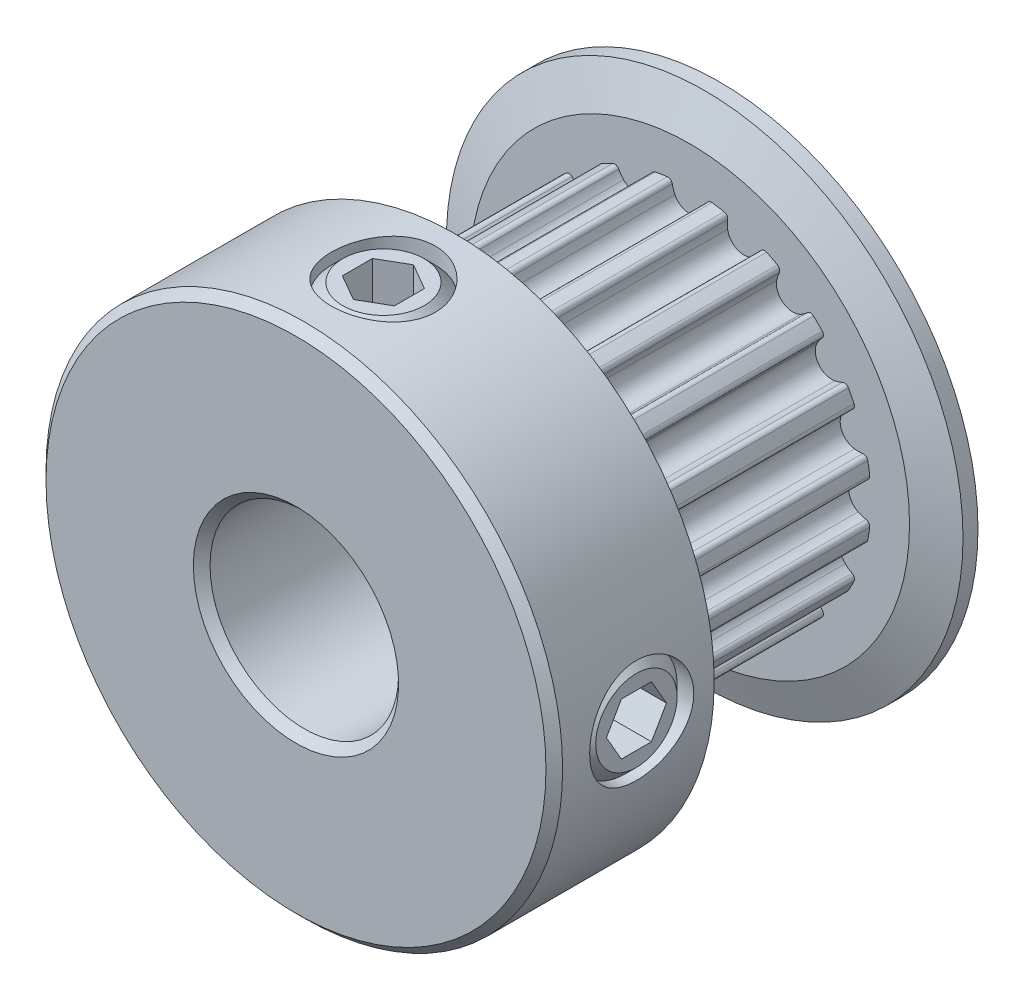
SolidWorks part; units mm, degrees
ref_plane "Front Plane" through (0, 0, 0) normal (0, 0, 1) x (1, 0, 0)
ref_plane "Top Plane" through (0, 0, 0) normal (0, 1, 0) x (1, 0, 0)
ref_plane "Right Plane" through (0, 0, 0) normal (1, 0, 0) x (0, 0, -1)
sketch "Sketch1" plane through (0, 0, 0) normal (0, 0, 1) x (1, 0, 0)
  line L1 (-1.7499, 5.3585) -> (1.7499, 5.3585) construction
  line L4 (0, 0) -> (0, 5.3585) construction
  line L5 (0, 5.3585) -> (0, 11.2045) construction
  line L6 (0, 6.3625) -> (1.9751, 6.0482) construction
  line L7 (1.9751, 6.0482) -> (2.6648, 5.8229) construction
  line L8 (1.9751, 6.0482) -> (1.7499, 5.3585) construction
  line L9 (-1.9751, 6.0482) -> (-1.7499, 5.3585) construction
  line L10 (-1.8963, 5.8067) -> (-2.841, 8.6995)
  line L11 (-2.841, 8.6995) -> (2.841, 8.6995)
  line L12 (2.841, 8.6995) -> (1.8963, 5.8067)
  circle A0 centre (0, 0) radius 6.3625 construction
  circle A1 centre (0, 0) radius 8.6995 construction
  circle A2 centre (0, 0) radius 6.1085 construction
  arc A3 (-0.4989, 5.6703) -> (0.4989, 5.6703) centre (0, 5.9135) ccw
  arc A4 (-0.4989, 5.6703) -> (-0.5855, 5.9387) centre (0.4, 6.1085) cw
  arc A5 (-1.8963, 5.8067) -> (-0.7518, 6.0621) centre (0, 0) cw
  arc A6 (-0.5855, 5.9387) -> (-0.7518, 6.0621) centre (-0.7333, 5.9132) ccw
  arc A7 (1.8963, 5.8067) -> (0.7518, 6.0621) centre (0, 0) ccw
  arc A8 (0.5855, 5.9387) -> (0.7518, 6.0621) centre (0.7333, 5.9132) cw
  arc A9 (0.4989, 5.6703) -> (0.5855, 5.9387) centre (-0.4, 6.1085) ccw
  point P6 (0, 20.9083)
  point P11 (0, 6.3625)
  point P13 (0, 8.6995)
  point P14 (0, 6.1085)
  dimension "D1" = 9.7038
  dimension "D2" = 4.842
sketch "Sketch2" plane through (0, 0, 0) normal (1, 0, 0) x (0, 0, -1)
  line L0 (-7.135, 3.175) -> (7.135, 3.175)
  line L1 (-7.135, 3.175) -> (-7.135, 8.6995)
  line L2 (-1.75, 8.6995) -> (-7.135, 8.6995)
  line L3 (-2.255, 3.175) -> (-2.255, 8.6995) construction
  line L4 (-2.255, 8.6995) -> (-1.245, 8.6995) construction
  line L5 (-1.245, 8.6995) -> (-1.245, 6.1085) construction
  line L6 (-1.245, 6.1085) -> (6.125, 6.1085)
  line L7 (6.125, 6.1085) -> (6.125, 8.6995) construction
  line L8 (6.125, 8.6995) -> (7.135, 8.6995) construction
  line L9 (7.135, 8.6995) -> (7.135, 3.175)
  line L10 (-7.135, 0) -> (7.135, 0) construction
  line L11 (6.63, 8.6995) -> (6.125, 7.404)
  line L12 (-1.245, 7.404) -> (-1.75, 8.6995)
  line L14 (-1.245, 7.404) -> (-1.245, 6.1085)
  line L15 (6.125, 6.1085) -> (6.125, 7.404)
  line L16 (6.63, 8.6995) -> (7.135, 8.6995)
  arc A0 (-1.245, 7.404) -> (-1.75, 8.6995) centre (-3.1592, 7.404) ccw construction
  arc A1 (6.125, 7.404) -> (6.63, 8.6995) centre (8.0392, 7.404) cw construction
  point P12 (-1.245, 7.404)
  point P14 (-1.75, 8.6995)
  point P20 (6.125, 7.404)
  point P21 (6.63, 8.6995)
  point P25 (6.125, 0)
  point P26 (-1.245, 0)
  dimension "OA" = 14.27
  dimension "Bore" = 6.35
  dimension "Outside Width" = 8.38
  dimension "Inside Width" = 7.37
revolve "Revolve1" add sketch "Sketch2" angle 360 mid plane about L10
sketch "Sketch3" plane through (0, 0, 0) normal (0, 0, 1) x (1, 0, 0)
  line L6 (2.841, 8.6995) -> (-2.841, 8.6995)
  line L7 (1.8963, 5.8067) -> (2.841, 8.6995)
  line L8 (-2.841, 8.6995) -> (-1.8963, 5.8067)
  line L9 (2.841, 8.6995) -> (-2.841, 8.6995)
  line L10 (1.8963, 5.8067) -> (2.841, 8.6995)
  line L11 (-2.841, 8.6995) -> (-1.8963, 5.8067)
  arc A8 (1.8963, 5.8067) -> (0.7518, 6.0621) centre (0, 0) ccw
  arc A9 (0.7518, 6.0621) -> (0.5855, 5.9387) centre (0.7333, 5.9132) ccw
  arc A10 (0.4989, 5.6703) -> (0.5855, 5.9387) centre (-0.4, 6.1085) ccw
  arc A11 (-0.4989, 5.6703) -> (0.4989, 5.6703) centre (0, 5.9135) ccw
  arc A12 (-0.5855, 5.9387) -> (-0.4989, 5.6703) centre (0.4, 6.1085) ccw
  arc A13 (-0.5855, 5.9387) -> (-0.7518, 6.0621) centre (-0.7333, 5.9132) ccw
  arc A14 (-0.7518, 6.0621) -> (-1.8963, 5.8067) centre (0, 0) ccw
  arc A15 (1.8963, 5.8067) -> (0.7518, 6.0621) centre (0, 0) ccw
  arc A16 (0.7518, 6.0621) -> (0.5855, 5.9387) centre (0.7333, 5.9132) ccw
  arc A17 (0.4989, 5.6703) -> (0.5855, 5.9387) centre (-0.4, 6.1085) ccw
  arc A18 (-0.4989, 5.6703) -> (0.4989, 5.6703) centre (0, 5.9135) ccw
  arc A19 (-0.5855, 5.9387) -> (-0.4989, 5.6703) centre (0.4, 6.1085) ccw
  arc A20 (-0.5855, 5.9387) -> (-0.7518, 6.0621) centre (-0.7333, 5.9132) ccw
  arc A21 (-0.7518, 6.0621) -> (-1.8963, 5.8067) centre (0, 0) ccw
  dimension "D1" = 0
extrude "Cut-Extrude1" cut sketch "Sketch3" against normal up to vertex (6.125 mm away) from vertex up to point (0, 6.1085, -6.125) starting at point (0, 6.1085, 1.245)
pattern_circular "CirPattern1" count 20 over 360 about axis through (0, 0, 7.135) along (0, 0, 1) of "Cut-Extrude1"
sketch "Sketch4" plane through (0, 0, 0) normal (1, 0, 0) x (0, -1, 0)
  line L0 (0, -1.245) -> (0, -7.135) construction
  line L1 (-3.175, -7.135) -> (3.175, -7.135) construction
  line L2 (7.404, -1.245) -> (-7.404, -1.245) construction
  circle A0 centre (0, -4.19) radius 1.7526
extrude "Cut-Extrude2" cut sketch "Sketch4" along normal through all
ref_plane "Plane1" through (0, 0, 4.19) normal (0, 0, 1) x (1, 0, 0)
sketch "Sketch5" plane through (0, 0, 4.19) normal (0, 0, 1) x (1, 0, 0)
  line L0 (0, 0) -> (0, 8.6995) construction
  line L1 (3.175, -1.3716) -> (3.175, 0)
  line L2 (3.556, -1.7526) -> (8.1401, -1.7526)
  line L3 (3.175, 0) -> (8.6995, 0) construction
  line L4 (3.175, 0) -> (8.5211, 0)
  line L5 (8.5211, 0) -> (8.5211, -1.3716)
  line L6 (3.556, -1.7526) -> (3.175, -1.3716)
  line L7 (8.5211, -1.3716) -> (8.1401, -1.7526)
  circle A0 centre (0, 0) radius 8.6995 construction
  circle A1 centre (0, 0) radius 3.175 construction
  point P2 (3.175, -1.7526)
  point P11 (8.5211, -1.7526)
revolve "Revolve2" add sketch "Sketch5" angle 360 mid plane about L4
sketch "Sketch6" plane through (8.5211, 5.3841, 0) normal (-1, 0, 0) x (0, -1, 0)
  line L1 (5.3841, 5.2019) -> (4.5078, 4.6959)
  line L2 (4.5078, 4.6959) -> (4.5078, 3.6841)
  line L3 (4.5078, 3.6841) -> (5.3841, 3.1781)
  line L4 (5.3841, 3.1781) -> (6.2604, 3.6841)
  line L5 (6.2604, 3.6841) -> (6.2604, 4.6959)
  line L6 (6.2604, 4.6959) -> (5.3841, 5.2019)
  circle A0 centre (5.3841, 4.19) radius 0.8763 construction
  dimension "D1" = 1.7526
extrude "Cut-Extrude3" cut sketch "Sketch6" along normal blind 1.3144
pattern_circular "CirPattern3" count 2 over 90 about axis through (0, 0, 7.135) along (0, 0, 1) of "Cut-Extrude2", "Revolve2", "Cut-Extrude3"
chamfer "Chamfer1" distance 0.2807 angle 45 2 edges at (3.175, 0, 7.135) (8.6995, 0, 7.135)
ref_axis "Center Axis 1" through (0, 0, -7.135) along (0, 0, 1)
ref_plane "Contact Plane 1" through (0, 0, 7.135) normal (0, 0, 1) x (1, 0, 0)
ref_plane "Contact Plane 2" through (0, 0, -7.135) normal (0, 0, -1) x (-1, 0, 0)
equation "\"D2@Sketch1\"= \"D1@Sketch1\" / 2"
equation "\"D1@Sketch6\" = \"Set Screw@Sketch4\" / 2"
equation "\"D1@Cut-Extrude3\" = \"D1@Sketch6\"*.75"
